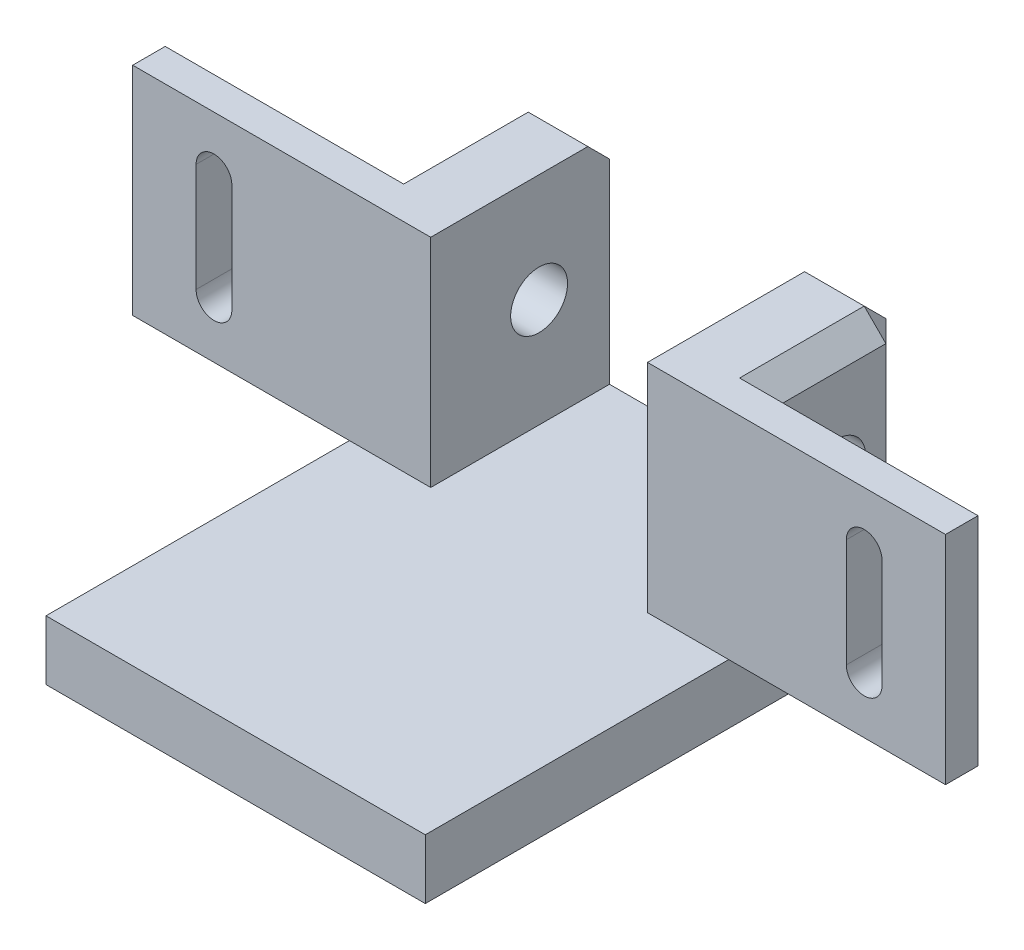
SolidWorks part; units mm, degrees
ref_plane "Front Plane" through (0, 0, 0) normal (0, 0, 1) x (1, 0, 0)
ref_plane "Top Plane" through (0, 0, 0) normal (0, 1, 0) x (1, 0, 0)
ref_plane "Right Plane" through (0, 0, 0) normal (1, 0, 0) x (0, 0, -1)
sketch "Sketch1" plane through (0, 0, 0) normal (1, 0, 0) x (0, 0, -1)
  line L0 (-10, -10) -> (6.5, -10)
  line L5 (-10, 10) -> (6.5, 10)
  line L7 (-10, -17.5) -> (6.5, -17.5)
  line L8 (6.5, 10) -> (6.5, -17.5)
  line L9 (-10, -10) -> (-38, -10)
  line L10 (-38, -10) -> (-38, -17.5)
  line L11 (-38, -17.5) -> (-10, -17.5)
  line L12 (6.5, 10) -> (10, 10) construction
  line L13 (10, 10) -> (10, -17.5) construction
  line L14 (10, -17.5) -> (6.5, -17.5) construction
  line L15 (-10, -10) -> (-10, 10)
  line L16 (-10, -17.5) -> (-10, -10)
  line L17 (-13, -10) -> (-13, -17.5) construction
  line L18 (-25.5, -10) -> (-25.5, -17.5) construction
  circle A0 centre (0, 0) radius 2.625
  circle A1 centre (0, 0) radius 5
  point P4 (-10, 0)
  point P6 (0, 0)
  dimension "D9" = 5.25
  dimension "D10" = 10
  dimension "D1" = 20
  dimension "D2" = 10
  dimension "D3" = 20
  dimension "D4" = 7.5
  dimension "D5" = 3.5
  dimension "D6" = 3
  dimension "D7" = 25
  dimension "D8" = 12.5
extrude "Boss-Extrude1" add sketch "Sketch1" along normal blind 7.5 from offset 10 contours L15 L0 L8 L5 | A1 A0 region at (0, 0, 9.7407) region at (0, 0, 4.8586)
extrude "Boss-Extrude2" add sketch "Sketch1<3>" against normal blind 7.5 from offset 10 separate body contours L15 L0 L8 L5 | A1 A0 region at (0, 0, 9.7407) region at (0, 0, 4.8586) offset against normal yes
sketch "Sketch1<3>" plane through (0, 0, 0) normal (1, 0, 0) x (0, 0, -1) same geometry as "Sketch1"
extrude "Boss-Extrude3" add sketch "Sketch1<4>" along normal up to surface (17.5 mm away) and the other way up to surface (17.5 mm away) contours L16 L7 L8 L0 | L11 L16 L9 L10 region at (0, -13.75, 24) region at (0, -13.75, 1.75) up to face at (17.5, 0, 1.75) other way up to face at (-17.5, 0, 1.75)
sketch "Sketch1<4>" plane through (0, 0, 0) normal (1, 0, 0) x (0, 0, -1) same geometry as "Sketch1"
sketch "Sketch4" plane through (0, 0, 10) normal (0, 0, 1) x (1, 0, 0)
  line L0 (-30, 5) -> (-30, -5) construction
  line L1 (17.5, 10) -> (37.5, 10)
  line L2 (17.5, 10) -> (17.5, -10)
  line L3 (17.5, -10) -> (37.5, -10)
  line L4 (37.5, 10) -> (37.5, -10)
  line L5 (-17.5, 10) -> (-37.5, 10)
  line L6 (-17.5, 10) -> (-17.5, -10)
  line L7 (-17.5, -10) -> (-37.5, -10)
  line L8 (-37.5, 10) -> (-37.5, -10)
  line L9 (-28.35, 5) -> (-28.35, -5)
  line L10 (-31.65, 5) -> (-31.65, -5)
  line L11 (0, -1000) -> (0, 49000) construction
  line L12 (30, 5) -> (30, -5) construction
  line L13 (28.35, 5) -> (28.35, -5)
  line L14 (31.65, 5) -> (31.65, -5)
  arc A0 (-28.35, 5) -> (-31.65, 5) centre (-30, 5) ccw
  arc A1 (-31.65, -5) -> (-28.35, -5) centre (-30, -5) ccw
  arc A2 (28.35, 5) -> (31.65, 5) centre (30, 5) cw
  arc A3 (31.65, -5) -> (28.35, -5) centre (30, -5) cw
  point P12 (-30, 0)
  point P24 (30, 0)
  dimension "D1" = 1.65
  dimension "D2" = 30
  dimension "D3" = 20
  dimension "D4" = 10
extrude "Boss-Extrude5" add sketch "Sketch4" against normal blind 5
sketch "Sketch2" plane through (0, -10, 0) normal (0, 1, 0) x (1, 0, 0)
  line L0 (-17.5, -10) -> (-40, -10)
  line L1 (-40, -10) -> (-40, -38)
  line L2 (-40, -38) -> (-17.5, -38)
  line L3 (-17.5, -10) -> (-17.5, -38)
  line L4 (0, -1000) -> (0, 49000) construction
  line L5 (17.5, -10) -> (17.5, -38)
  line L6 (40, -38) -> (17.5, -38)
  line L7 (40, -10) -> (40, -38)
  line L8 (17.5, -10) -> (40, -10)
  line L9 (-30, -29.25) -> (-30, -21.75) construction
  line L10 (-31.625, -29.25) -> (-31.625, -21.75)
  line L11 (-28.375, -29.25) -> (-28.375, -21.75)
  line L12 (30, -29.25) -> (30, -21.75) construction
  line L13 (31.625, -29.25) -> (31.625, -21.75)
  line L14 (28.375, -29.25) -> (28.375, -21.75)
  arc A0 (-31.625, -29.25) -> (-28.375, -29.25) centre (-30, -29.25) ccw
  arc A1 (-28.375, -21.75) -> (-31.625, -21.75) centre (-30, -21.75) ccw
  arc A2 (31.625, -29.25) -> (28.375, -29.25) centre (30, -29.25) cw
  arc A3 (28.375, -21.75) -> (31.625, -21.75) centre (30, -21.75) cw
  point P6 (-30, -25.5)
  point P13 (30, -25.5)
  point P14 (-30, -25.5)
  point P24 (30, -25.5)
  line M6 (-17.5, -10) -> (-17.5, -38)
  line M8 (17.5, -38) -> (17.5, -10)
  dimension "D4" = 1.625
  dimension "D1" = 12.5
  dimension "D2" = 60
  dimension "D3" = 10
  dimension "D5" = 7.5
extrude "Boss-Extrude4" [suppressed] add sketch "Sketch2" against normal up to surface (7.5 mm away) contours L1 L2 L0 M6 | L8 L6 L7 M8 up to face at (0, -17.5, 15.75)
chamfer "Chamfer1" distance 2 angle 45 16 edges at (-17.5, 10, -0.75) (17.5, 10, -0.75) (-13.75, 10, -6.5) (13.75, 10, -6.5) (-17.5, -3.75, -6.5) (17.5, -3.75, -6.5) (17.5, -17.5, 15.75) (0, -17.5, -6.5) (-17.5, -17.5, 15.75) (0, -17.5, 38) (27.5, -10, 5) (37.5, 0, 5) (27.5, 10, 5) (-27.5, -10, 5) (-37.5, 0, 5) (-27.5, 10, 5)
equation "\"D8@Sketch1\"=\"D7@Sketch1\"/2"
